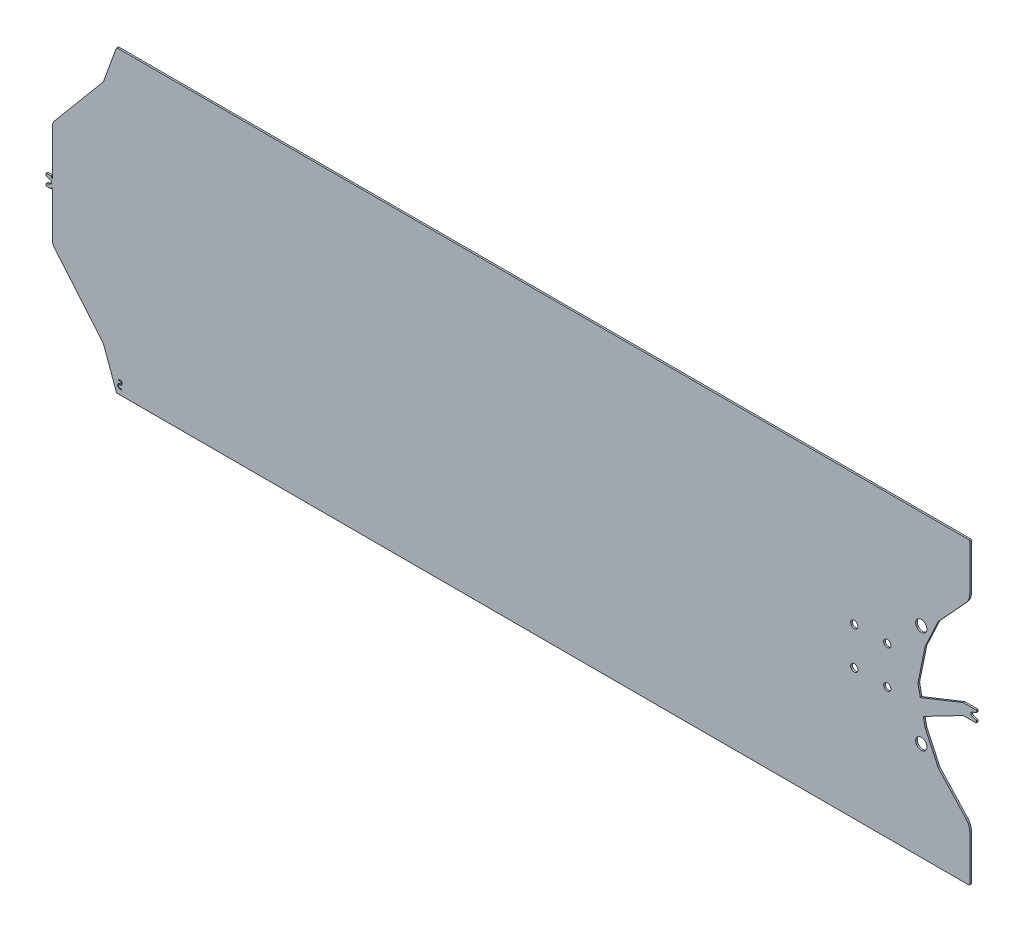
SolidWorks part; units mm, degrees
extrude "Base-Extrude" add sketch "Sketch1" along normal blind 5
sketch "Sketch1" plane through (0, 0, 0) normal (0, 0, 1) x (1, 0, 0)
  line L0 (0, 450.25) -> (0, 311.8051)
  line L1 (81.8142, 0) -> (-2780, 0) construction
  line L2 (-3, 453.25) -> (-2584.0976, 453.25)
  line L3 (-2625.6319, -344.9069) -> (-2586.9167, -451.2761)
  line L4 (-2627.3684, 341.8993) -> (-2775.3209, 165.5763)
  line L5 (-2780, 152.7206) -> (-2780, 0)
  line L6 (-2625.6319, 344.9069) -> (-2586.9167, 451.2761)
  line L7 (-2792.0623, 0) -> (-2797, 0)
  line L8 (-2800, -3) -> (-2800, -12.6577)
  line L9 (-2797.7276, -15.5681) -> (-2782.2724, -19.4319)
  line L10 (-2780, -1) -> (-2780, 0)
  line L11 (-2780, 109.75) -> (0, 109.75) construction
  line L12 (-2625.871, 344.25) -> (0, 344.25) construction
  line L13 (-96.1805, 190.6024) -> (-134.7813, 107.8227)
  line L14 (-135.5174, -105.5902) -> (-148.8619, -40)
  line L15 (-144.7606, 0) -> (17, 0)
  line L16 (20, -3) -> (20, -17.3344)
  line L17 (-3, -453.25) -> (-2584.0976, -453.25)
  line L18 (-2780, -152.7206) -> (-2780, -22.3423)
  line L19 (0, -311.8051) -> (0, -450.25)
  line L20 (17.3529, -20.3135) -> (-148.8619, -40)
  line L21 (-10.5089, 284.7815) -> (-94.4902, 193.1321)
  line L22 (-96.1805, -190.6024) -> (-134.7813, -107.8227)
  line L23 (-10.5089, -284.7815) -> (-94.4902, -193.1321)
  line L25 (-2627.3684, -341.8993) -> (-2775.3209, -165.5763)
  line L27 (-135.5174, 105.5902) -> (-154.5599, 11.9937)
  circle A0 centre (-147, 154.75) radius 17.125
  arc A1 (-2586.9167, 451.2761) -> (-2584.0976, 453.25) centre (-2584.0976, 450.25) cw
  arc A2 (-2780, -152.7206) -> (-2775.3209, -165.5763) centre (-2760, -152.7206) ccw
  arc A3 (-2625.6319, -344.9069) -> (-2627.3684, -341.8993) centre (-2635.0288, -348.3271) ccw
  arc A4 (-2780, -1) -> (-2787.5832, -2.7778) centre (-2784, -1) cw
  arc A5 (-2787.5832, -2.7778) -> (-2792.0623, 0) centre (-2792.0623, -5) ccw
  arc A6 (-2586.9167, -451.2761) -> (-2584.0976, -453.25) centre (-2584.0976, -450.25) ccw
  arc A7 (-2625.6319, 344.9069) -> (-2627.3684, 341.8993) centre (-2635.0288, 348.3271) cw
  circle A8 centre (-2560, 398.25) radius 17.625 construction
  circle A9 centre (-2460, 398.25) radius 17.625 construction
  circle A10 centre (-2460, -398.25) radius 17.625 construction
  circle A11 centre (-2560, -398.25) radius 17.625 construction
  arc A12 (-144.7606, 0) -> (-154.5599, 11.9937) centre (-144.7606, 10) cw
  arc A13 (-94.4902, 193.1321) -> (-96.1805, 190.6024) centre (-87.1174, 186.3762) ccw
  arc A14 (-2780, 152.7206) -> (-2775.3209, 165.5763) centre (-2760, 152.7206) cw
  arc A15 (0, 450.25) -> (-3, 453.25) centre (-3, 450.25) ccw
  arc A16 (0, 311.8051) -> (-10.5089, 284.7815) centre (-40, 311.8051) cw
  arc A17 (-135.5174, 105.5902) -> (-134.7813, 107.8227) centre (-125.7182, 103.5965) cw
  arc A18 (-134.7813, -107.8227) -> (-135.5174, -105.5902) centre (-125.7182, -103.5965) cw
  arc A19 (-2800, -3) -> (-2797, 0) centre (-2797, -3) cw
  arc A20 (-2797.7276, -15.5681) -> (-2800, -12.6577) centre (-2797, -12.6577) cw
  arc A21 (-96.1805, -190.6024) -> (-94.4902, -193.1321) centre (-87.1174, -186.3762) ccw
  circle A22 centre (-2360, 398.25) radius 17.625 construction
  arc A23 (0, -311.8051) -> (-10.5089, -284.7815) centre (-40, -311.8051) ccw
  arc A24 (-3, -453.25) -> (0, -450.25) centre (-3, -450.25) ccw
  arc A25 (-2782.2724, -19.4319) -> (-2780, -22.3423) centre (-2783, -22.3423) cw
  arc A26 (20, -3) -> (17, 0) centre (17, -3) ccw
  arc A27 (20, -17.3344) -> (17.3529, -20.3135) centre (17, -17.3344) cw
  circle A28 centre (-147, -154.75) radius 17.125
  circle A29 centre (-250, 57) radius 11
  circle A30 centre (-350, 57) radius 11
  circle A31 centre (-250, -57) radius 11
  circle A32 centre (-350, -57) radius 11
  circle A33 centre (-2360, -398.25) radius 17.625 construction
  point P6 (-2586.1983, 453.25)
  point P45 (-2626.235, 343.25)
  point P47 (-157, 0)
  point P48 (-95.53, 191.9973)
  point P60 (-2780, 160)
  point P70 (0, 296.25)
  point P73 (-135.2815, 106.75)
  point P78 (-2800, 0)
  point P84 (-135.2815, -106.75)
  point P88 (0, -296.25)
  point P92 (-2800, -15)
  point P95 (-2780, -20)
  point P100 (20, -20)
  point P105 (-95.53, -191.9973)
  dimension "D1" = 5
  dimension "D2" = 4
  dimension "D9" = 42.5
  dimension "D10" = 25
  dimension "D11" = 147
  dimension "D12" = 10
  dimension "D27" = 35.25
  dimension "D28" = 100
  dimension "D35" = 3
  dimension "D42" = 114
  dimension "D43" = 157
  dimension "D45" = 100
  dimension "D46" = 11.5
  dimension "D47" = 3
  dimension "D30" = 10
  dimension "D31" = 40
  dimension "D22" = 100
  dimension "D29" = 3
  dimension "D34" = 3
  dimension "D37" = 220
  dimension "D18" = 40
  dimension "D7" = 34.25
  dimension "D23" = 20
  dimension "D15" = 3
  dimension "D41" = 22
  dimension "D48" = 10
  dimension "D3" = 20
  dimension "D4" = 15
  dimension "D5" = 20
  dimension "D6" = 5
  dimension "D8" = 40
  dimension "D13" = 109.75
  dimension "D14" = 20
  dimension "D16" = 45
  dimension "D17" = 48
  dimension "D19" = 20
  dimension "D20" = 160
  dimension "D21" = 110
  dimension "D24" = 109
  dimension "D25" = 234.5
  dimension "D26" = 906.5
  dimension "D32" = 55
  dimension "D33" = 20
  dimension "D36" = 2780
  dimension "D38" = 54
  dimension "D39" = 250
  dimension "D40" = 43.4294
  dimension "D50" = 52.75
bend "FlatBend2" bend angle 65 parameters "D1"=0, "D5"=2
bend "FlatBend1" bend angle 65 parameters "D1"=0, "D5"=1
bend "FlatBend5" bend angle 65 parameters "D1"=0, "D5"=5
bend "FlatBend4" bend angle 65 parameters "D1"=0, "D5"=4, "RD1"=353.6842, "RD2"=5
ref_plane "Front" through (0, 0, 0) normal (0, 0, 1) x (1, 0, 0)
ref_plane "Top" through (0, 0, 0) normal (0, 1, 0) x (1, 0, 0)
ref_plane "Right" through (0, 0, 0) normal (1, 0, 0) x (0, 0, -1)
sheet metal parameters "Sheet-Metal1" parameters "D1"=16
flatten bends "Flatten-Bends1" parameters "D1"=8
sketch "Sharp-Sketch1" plane through (0, 0, 5) normal (0, 0, 1) x (1, 0, 0)
sketch "Sketch5" plane through (0, 0, 5) normal (0, 0, 1) x (1, 0, 0)
  line L1 (-2579.25, -414.25) -> (-2573, -414.25)
  line L2 (-2780, -152.7206) -> (-2780, -22.3423) construction
  line L3 (-3, -453.25) -> (-2584.0976, -453.25) construction
  line L20 (-2570, -417.25) -> (-2570, -423.25)
  line L22 (-2573, -426.25) -> (-2575.5, -426.25)
  line L23 (-2575.5, -435.75) -> (-2571, -435.75)
  line L24 (-2570, -436.75) -> (-2570, -437.25)
  line L25 (-2571, -438.25) -> (-2575.5, -438.25)
  line L26 (-2575.5, -423.75) -> (-2573.5, -423.75)
  line L27 (-2572.5, -422.75) -> (-2572.5, -417.75)
  line L28 (-2573.5, -416.75) -> (-2579.25, -416.75)
  line L29 (-2580.25, -415.75) -> (-2580.25, -415.25)
  arc A0 (-2575.5, -426.25) -> (-2575.5, -435.75) centre (-2575.5, -431) ccw
  arc A1 (-2575.5, -438.25) -> (-2575.5, -423.75) centre (-2575.5, -431) cw
  arc A2 (-2572.5, -417.75) -> (-2573.5, -416.75) centre (-2573.5, -417.75) ccw
  arc A3 (-2570, -437.25) -> (-2571, -438.25) centre (-2571, -437.25) cw
  arc A4 (-2571, -435.75) -> (-2570, -436.75) centre (-2571, -436.75) cw
  arc A5 (-2579.25, -416.75) -> (-2580.25, -415.75) centre (-2579.25, -415.75) cw
  arc A6 (-2579.25, -414.25) -> (-2580.25, -415.25) centre (-2579.25, -415.25) ccw
  arc A7 (-2573.5, -423.75) -> (-2572.5, -422.75) centre (-2573.5, -422.75) ccw
  arc A8 (-2573, -414.25) -> (-2570, -417.25) centre (-2573, -417.25) cw
  arc A9 (-2570, -423.25) -> (-2573, -426.25) centre (-2573, -423.25) cw
  dimension "D5" = 2.5
  dimension "D6" = 1
  dimension "D8" = 12
  dimension "D12" = 5.5
  dimension "D4" = 1
  dimension "D7" = 3
  dimension "D2" = 210
  dimension "D3" = 15
  dimension "D10" = 2.5
  dimension "D11" = 2.5
  dimension "D13" = 24
extrude "Skåret 5 tal" cut sketch "Sketch5" against normal through all
sketch "Sketch2" plane through (0, 0, 5) normal (0, 0, 1) x (1, 0, 0)
  line L0 (0, -453.25) -> (-2780, -453.25)
  line L1 (0, 453.25) -> (0, 58.7919)
  line L2 (-2780, 453.25) -> (0, 453.25)
  line L3 (-2780, 453.25) -> (-2780, -453.25)
  line L5 (-3, 453.25) -> (-2584.0976, 453.25) construction
  line L8 (-145.0386, -58.7919) -> (0, -58.7919)
  line L9 (690.6763, 0) -> (-641.7821, 0) construction
  line L11 (0, -58.7919) -> (0, -453.25)
  line L12 (-145.0386, 58.7919) -> (0, 58.7919)
  line L13 (-2780, 152.7206) -> (-2780, 0) construction
  line L14 (-3, -453.25) -> (-2584.0976, -453.25) construction
  line L15 (-135.5174, 105.5902) -> (-154.5599, 11.9937) construction
  line L18 (-145.0386, 58.7919) -> (-156.5944, 1.9937)
  line L21 (-135.5174, -105.5902) -> (-148.8619, -40) construction
  line L23 (-145.0386, -58.7919) -> (-156.5944, -1.9937)
  arc A0 (-156.5944, -1.9937) -> (-156.5944, 1.9937) centre (-146.7951, 0) cw
  dimension "D3" = 10
extrude "Bortskæring af bukkestop" cut sketch "Sketch2" against normal blind 5 flip side to cut
process bends "Process-Bends1" [suppressed]
sketch "Flat-Sketch1" plane through (0, 0, 5) normal (0, 0, 1) x (1, 0, 0)
  line L0 (-2625.871, 344.25) -> (0, 344.25) construction
  line L1 (-2780, 109.75) -> (0, 109.75) construction
  line L11 (81.8142, 0) -> (-2780, 0) construction
  line L12 (-2683.6943, 344.25) -> (76.9875, 344.25) construction
  line L13 (-2890, 109.75) -> (0, 109.75) construction
  line L14 (81.8142, 0) -> (-2808.3427, 0) construction
  line L15 (-2890, -109.75) -> (0, -109.75) construction
  line L16 (-2683.6943, -344.25) -> (76.9875, -344.25) construction
  point P10 (-1165, -293)
  point P11 (-1456.9413, 227)
bend "FlatBend3" bend angle 50 parameters "D1"=0, "D5"=3
sketch "Tværsnitsmål" [suppressed] plane through (0, 0, 0) normal (1, 0, 0) x (0, 0, -1)
  line L2 (-195.5996, 352.9268) -> (-108.9164, 393.3478) construction
  line L3 (-98.8082, 393.3478) -> (-12.125, 352.9268) construction
  line L4 (-94.9873, 62.4339) -> (-12.125, 101.0732) construction
  line L5 (-103.8623, 58.2954) -> (-12.125, 101.0732)
  line L6 (0, 333.8943) -> (0, 165.5763) construction
  line L7 (0, 333.8943) -> (0, 165.5763)
  line L8 (-195.5996, 101.0732) -> (-112.7373, 62.4339) construction
  line L9 (-195.5996, 101.0732) -> (-103.8623, 58.2954)
  line L11 (-207.7246, 302.7277) -> (-207.7246, 163.7157)
  line L12 (-207.7246, 284.7815) -> (-207.7246, 193.1321) construction
  point P0 (-103.8623, 395.7046)
  dimension "D1" = 305.7966
  dimension "D2" = 50
  dimension "D3" = 65
  dimension "D4" = 207.7246
  dimension "D5" = 337.4092
sketch "Bukkelinier" plane through (0, 0, 0) normal (0, 0, -1) x (-1, 0, 0)
  line L0 (2683.6943, 344.25) -> (-76.9875, 344.25) construction
  line L1 (2890, 109.75) -> (0, 109.75) construction
  line L2 (-81.8142, 0) -> (2808.3427, 0) construction
  line L3 (2890, -109.75) -> (0, -109.75) construction
  line L4 (2683.6943, -344.25) -> (-76.9875, -344.25) construction
  line L5 (2625.8977, 344.25) -> (0, 344.25) construction
  line L6 (2780, 109.75) -> (133.7127, 109.75) construction
  line L7 (0, 0) -> (2808.3427, 0) construction
  line L8 (2780, -109.75) -> (134.9432, -109.75) construction
  line L9 (2625.3959, -344.25) -> (0, -344.25) construction
  line L11 (2627.3684, -341.8993) -> (2775.3209, -165.5763) construction
  line L12 (0, 450.25) -> (0, 311.8051) construction
  line L14 (0, -311.8051) -> (0, -450.25) construction
  line L15 (2780, -152.7206) -> (2780, 152.7206) construction
  arc A0 (2625.6319, 344.9069) -> (2627.3684, 341.8993) centre (2635.0288, 348.3271) ccw construction
sketch "Sketch4" [suppressed] plane through (0, 0, 0) normal (0, 1, 0) x (1, 0, 0)
  line L0 (-2780, -103.8623) -> (0, -103.8623)
  line L1 (-2780, -94.9873) -> (-2780, -112.7373) construction
split line "Split Line1" [suppressed]
ref_plane "Symmetriplan" [suppressed] through (0, 0, 103.8623) normal (0, 0, -1) x (-1, 0, 0)
ref_plane "Horisontalt plan - overside" [suppressed] through (0, 60.4663, 0) normal (0, 1, 0) x (-1, 0, 0)
sketch "Sketch6" plane through (0, 0, 5) normal (0, 0, 1) x (1, 0, 0)
  line L0 (0, 0) -> (-2789, 0) construction
  line L1 (-2786.9479, 5.6382) -> (-2799.342, 10.1493)
  line L2 (-2800, 11.0889) -> (-2800, 16)
  line L3 (-2799, 17) -> (-2786, 17)
  line L4 (-2784, 15) -> (-2784, 14.5)
  line L5 (-2780, -152.7206) -> (-2780, 152.7206) construction
  line L6 (-2780, 14.5) -> (-2780, -14.5)
  line L7 (-2784, -15) -> (-2784, -14.5)
  line L8 (-2799, -17) -> (-2786, -17)
  line L9 (-2800, -11.0889) -> (-2800, -16)
  line L10 (-2786.9479, -5.6382) -> (-2799.342, -10.1493)
  line L11 (6.9479, 5.6382) -> (19.342, 10.1493)
  line L12 (20, 11.0889) -> (20, 16)
  line L13 (19, 17) -> (-19.4245, 17)
  line L14 (20, -11.0889) -> (20, -16)
  line L15 (6.9479, -5.6382) -> (19.342, -10.1493)
  line L16 (19, -17) -> (-19.2672, -17)
  line L17 (0, 450.25) -> (0, 311.8051) construction
  line L18 (-135.5174, -105.5902) -> (-156.5944, -1.9937) construction
  line L19 (-140.7747, -79.75) -> (-149.93, -34.75)
  line L20 (-149.93, -34.75) -> (-20.5346, 16.7871)
  line L21 (-140.7747, -79.75) -> (-20.6503, -17.3379)
  line L22 (-2780, -109.75) -> (-134.9432, -109.75) construction
  arc A0 (-2786.9479, -5.6382) -> (-2786.9479, 5.6382) centre (-2789, 0) ccw
  arc A1 (-2784, 14.5) -> (-2780, 14.5) centre (-2782, 14.5) ccw
  arc A2 (-2784, -14.5) -> (-2780, -14.5) centre (-2782, -14.5) cw
  arc A3 (-2800, 16) -> (-2799, 17) centre (-2799, 16) cw
  arc A4 (-2799.342, 10.1493) -> (-2800, 11.0889) centre (-2799, 11.0889) cw
  arc A5 (-2800, -11.0889) -> (-2799.342, -10.1493) centre (-2799, -11.0889) cw
  arc A6 (-2799, -17) -> (-2800, -16) centre (-2799, -16) cw
  arc A7 (-2786, 17) -> (-2784, 15) centre (-2786, 15) cw
  arc A8 (-2784, -15) -> (-2786, -17) centre (-2786, -15) cw
  arc A9 (6.9479, -5.6382) -> (6.9479, 5.6382) centre (9, 0) cw
  arc A10 (20, 16) -> (19, 17) centre (19, 16) ccw
  arc A11 (19.342, 10.1493) -> (20, 11.0889) centre (19, 11.0889) ccw
  arc A12 (20, -11.0889) -> (19.342, -10.1493) centre (19, -11.0889) ccw
  arc A13 (20, -16) -> (19, -17) centre (19, -16) cw
  arc A14 (-19.4245, 17) -> (-20.5346, 16.7871) centre (-19.4245, 14) ccw
  arc A15 (-19.2672, -17) -> (-20.6503, -17.3379) centre (-19.2672, -20) ccw
  point P3 (-2780, 0)
  point P22 (-2800, 17)
  point P25 (-2800, 10.3887)
  point P28 (-2800, -10.3887)
  point P31 (-2800, -17)
  point P34 (-2784, 17)
  point P37 (-2784, -17)
  point P57 (20, 17)
  point P60 (20, 10.3887)
  point P63 (20, -10.3887)
  point P66 (20, -17)
  point P69 (-20, 17)
  point P72 (-20, -17)
  dimension "D1" = 2
  dimension "D2" = 6
  dimension "D8" = 1
  dimension "D9" = 2
  dimension "D10" = 6
  dimension "D18" = 1
  dimension "D19" = 3
  dimension "D3" = 11
  dimension "D4" = 40
  dimension "D5" = 34
  dimension "D6" = 29
  dimension "D7" = 20
  dimension "D11" = 11
  dimension "D12" = 34
  dimension "D13" = 40
  dimension "D14" = 20
  dimension "D15" = 40
  dimension "D16" = 30
  dimension "D17" = 45
extrude "Bukkestop - Farina" add sketch "Sketch6" against normal blind 5
